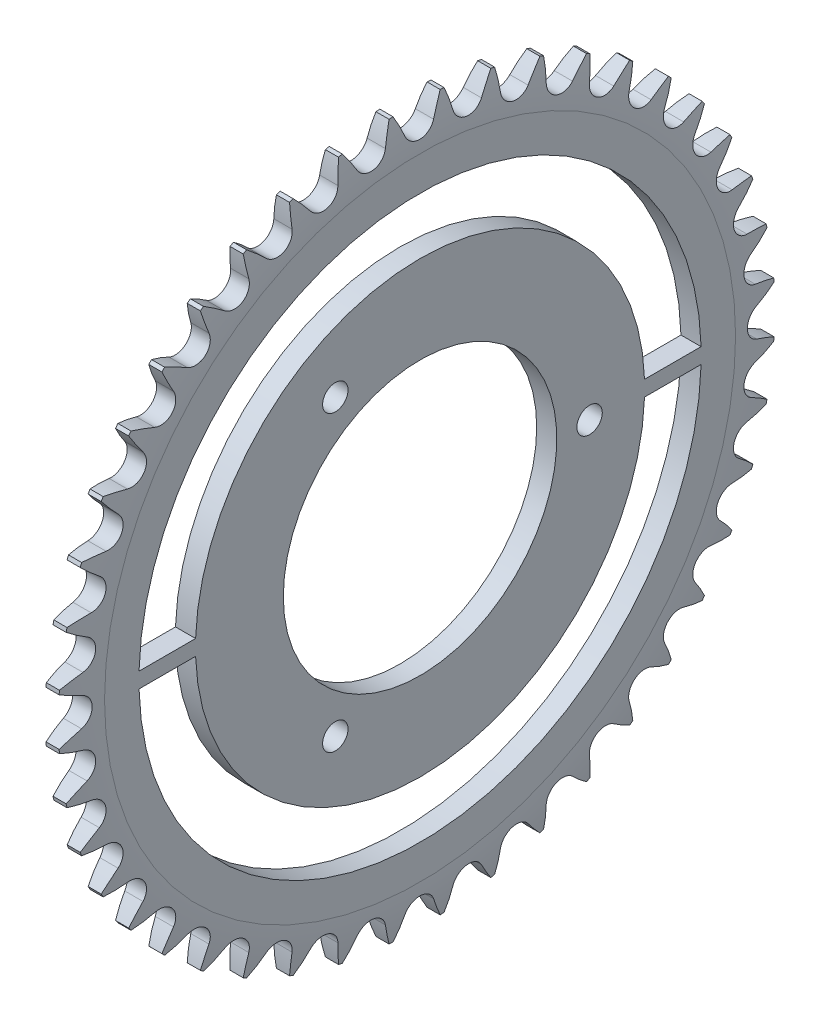
SolidWorks part; units mm, degrees
material "6061-T6 (SS)"
ref_plane "Plane1" through (0, 0, 0) normal (0, 0, 1) x (1, 0, 0)
ref_plane "Plane2" through (0, 0, 0) normal (0, 1, 0) x (1, 0, 0)
ref_plane "Plane3" through (0, 0, 0) normal (1, 0, 0) x (0, 0, -1)
sketch "Clipboard" plane through (0, 0, 0) normal (0, 1, 0) x (1, 0, 0)
  line L0 (0, 0) -> (4.166, -4.7924)
  line L1 (-15, 0) -> (100, 0) construction
  line L2 (0, 0) -> (-0.301, 0.3402)
  line L3 (0, 0) -> (-33.1636, 12.6754)
  line L4 (0, 0) -> (2.23, 2.1534)
  line L5 (0, 0) -> (-46.8476, -17.4728)
  line L6 (0, 0) -> (-2.1647, -1.4605)
  line L7 (-0.301, 0.3402) -> (35.1317, 35.773)
  line L8 (-76.2, 38.1) -> (-71.9, 38.1)
  line L9 (-73.4321, 41.7084) -> (-72.837, 41.7846)
  line L10 (-72.9336, 12.3402) -> (-58.5536, 12.3402)
  circle A0 centre (0, 0) radius 1.9875
  circle A1 centre (0, 0) radius 37.5
  circle A2 centre (0, 0) radius 37.5
  dimension "Num_teeth" = 44
  dimension "Thickness" = 2.6113
ref_axis "Axis1" through (0, 0, 0) along (1, 0, 0)
sketch "BasProSke" plane through (0, 0, 0) normal (0, 1, 0) x (1, 0, 0)
  line L0 (-10, 0) -> (60, 0) construction
  line L1 (0, 0) -> (0, 40.9511)
  line L2 (0, 0) -> (2.6113, 0)
  line L3 (2.6113, 0) -> (2.6113, 40.9511)
  line L4 (2.157, 46.4869) -> (0.4543, 46.4869)
  arc A0 (0, 40.9511) -> (0.4543, 46.4869) centre (33.9554, 40.9511) cw
  arc A1 (2.6113, 40.9511) -> (2.157, 46.4869) centre (-31.3441, 40.9511) ccw
  dimension "Thickness" = 2.6113
  dimension "Diameter" = 92.9739
  dimension "D1" = 5.5358
revolve "Base-Revolve" add sketch "BasProSke" angle 360 about L0
sketch "TooCutSke" plane through (0, 0, 0) normal (1, 0, 0) x (0, 0, -1)
  line L0 (0, 44.5256) -> (1.8738, 43.8054) construction
  line L1 (0, 0) -> (0, 107) construction
  line L2 (0, 44.5256) -> (-10, 44.5256) construction
  line L3 (0, 44.5256) -> (-1.8738, 43.8054) construction
  arc A0 (1.8738, 43.8054) -> (3.332, 46.8687) centre (22.3553, 35.934) cw
  arc A1 (1.8738, 43.8054) -> (-1.8738, 43.8054) centre (0, 44.5256) cw
  arc A2 (-1.8738, 43.8054) -> (-3.332, 46.8687) centre (-22.3553, 35.934) ccw
  arc A3 (3.332, 46.8687) -> (-3.332, 46.8687) centre (0, 0) ccw
extrude "ToothCut" cut sketch "TooCutSke" along normal through all
pattern_circular "TeethCuts" count 45 every 8.182 about axis through (-10, 0, 0) along (1, 0, 0) of "ToothCut"
ref_plane "FarPln" through (2.6113, 0, 0) normal (1, 0, 0) x (0, 0, -1)
sketch "BorSke" plane through (0, 0, 0) normal (1, 0, 0) x (0, 0, -1)
  circle A0 centre (0, 0) radius 17.75
  dimension "Diameter" = 35.5
extrude "Bore" cut sketch "BorSke" along normal mid plane 100.219
sketch "Sketch1" plane through (2.6113, 0, 0) normal (1, 0, 0) x (0, 0, -1)
  circle A0 centre (-11, 19.0526) radius 1.65
  circle A1 centre (22, 0) radius 1.65
  circle A2 centre (-11, -19.0526) radius 1.65
  point P10 (0, 0)
  point P19 (0, 0)
  dimension "D2" = 3.3
  dimension "D1" = 22
  dimension "D4" = 3
extrude "Cut-Extrude1" cut sketch "Sketch1" against normal blind 10
sketch "Sketch3" plane through (0, 0, 0) normal (-1, 0, 0) x (0, 0, 1)
  circle A0 centre (0, 0) radius 46.4869
  dimension "D1" = 92.9739
sketch "Sketch4" plane through (2.6113, 0, 0) normal (1, 0, 0) x (0, 0, -1)
  line L1 (0, 0) -> (29.15, 0) construction
  circle A0 centre (0, 0) radius 36.4869
  circle A1 centre (0, 0) radius 46.4869 construction
  circle A2 centre (0, 0) radius 29.15
  dimension "D1" = 10
  dimension "D2" = 29.15
extrude "Cut-Extrude2" cut sketch "Sketch4" against normal through all
sketch "Sketch5" plane through (2.6113, 0, 0) normal (1, 0, 0) x (0, 0, -1)
  line L1 (29.1328, 1) -> (36.4869, 1)
  line L2 (29.1328, 1) -> (29.1328, -1)
  line L3 (29.1328, -1) -> (36.4869, -1)
  line L4 (36.4869, 1) -> (36.4869, -1)
  circle A0 centre (0, 0) radius 29.15 construction
  circle A1 centre (0, 0) radius 36.4869 construction
  point P8 (29.1328, 0)
  dimension "D1" = 2
extrude "Boss-Extrude1" add sketch "Sketch5" against normal up to surface (2.6113 mm away) up to face at (0, 0, -17.75)
pattern_circular "CirPattern2" count 2 over 360 about axis through (0, 0, 0) along (1, 0, 0) of "Boss-Extrude1" reverse direction yes
equation "' \"Pitch@Clipboard\" = 12.7"
equation "' \"Num_strands@Clipboard\" = 1"
equation "' \"Num_teeth@Clipboard\" = 9"
equation "' \"Hub_dia@Clipboard\" = 50"
equation "' \"Overall_len@Clipboard\" = 3"
equation "' \"Diameter@BorSke\" = 12"
equation "' \"T_dim@Clipboard\" = 1"
equation "' \"Width@KeySke\" = 2"
equation "' \"Dr@Clipboard\" = 7.95"
equation "' \"Face_width@Clipboard\" = 7.3"
equation "' \"Side_radius@Clipboard\" = 12.7"
equation "' \"Side_relief@Clipboard\" = 1.27"
equation "' \"Transv_pitch@Clipboard\" = 14.38"
equation "' \"Show_teeth@Clipboard\" = 9"
equation "' \"Fillet_rad@Clipboard\" = 0.6"
equation "' \"Plate_wid@Clipboard\" = 12"
equation "\"MHD@Clipboard\" = \"Pitch@Clipboard\" * (1.0 / tan(3.14159265 / \"Num_teeth@Clipboard\" )) - 1.05 * \"Plate_wid@Clipboard\" - 2.0 * \"Fillet_rad@Clipboard\" - 1.0"
equation "\"OAL@Clipboard\" = \"Thickness@Clipboard\" + 2 * \"Fillet_rad@Clipboard\" + 1"
equation "\"MHD@Clipboard\" = ((sgn( \"MHD@Clipboard\" - \"Hub_dia@Clipboard\" )-1)*( \"MHD@Clipboard\" - \"Hub_dia@Clipboard\" ))/-2+ \"Hub_dia@Clipboard\""
equation "\"OAL@Clipboard\" = ((sgn( \"OAL@Clipboard\" - \"Overall_len@Clipboard\" )+1)*( \"OAL@Clipboard\" - \"Overall_len@Clipboard\" ))/2 + \"Overall_len@Clipboard\" + 0.0005"
equation "\"Num_teeth@TeethCuts\"=int( \"Num_teeth@Clipboard\" ) + 1"
equation "\"Num_teeth@TeethCuts\" = ((sgn( \"Num_teeth@TeethCuts\" - \"Num_teeth@Clipboard\" )-1)*( \"Num_teeth@TeethCuts\" - \"Num_teeth@Clipboard\" ))/-2+ \"Num_teeth@Clipboard\""
equation "\"Angle@TeethCuts\" = 360.0 / \"Num_teeth@Clipboard\""
equation "\"Seat_radius@TooCutSke\" = ( \"Pitch@Clipboard\" / 2.0) / sin(3.14159265 / \"Num_teeth@Clipboard\" ) - \"Dr@Clipboard\" / 2.0 + \"Dr@Clipboard\" * 0.505"
equation "\"R1@TooCutSke\"  = \"Dr@Clipboard\" * 0.505"
equation "\"X@TooCutSke\" = 140.0 - (90.0 / \"Num_teeth@Clipboard\")"
equation "\"R2@TooCutSke\" = 0.12 * \"Dr@Clipboard\" * ( \"Num_teeth@Clipboard\" + 2.0)"
equation "\"Overcut@TooCutSke\" = 0.5 + 0.625 * \"Pitch@Clipboard\" - 0.5 * \"Dr@Clipboard\"  +  \"Pitch@Clipboard\" / 2.0 / sin(3.14159265 / \"Num_teeth@Clipboard\" )"
equation "\"Diameter@BasProSke\" = 2.0 * ( 0.625 * \"Pitch@Clipboard\" - 0.5 * \"Dr@Clipboard\"  +  \"Pitch@Clipboard\" / 2.0 / sin(3.14159265 / \"Num_teeth@Clipboard\" ))"
equation "\"Thickness@BasProSke\"  = \"Thickness@Clipboard\""
equation "\"G1@BasProSke\"=\"Thickness@Clipboard\" * (127/730)"
equation "\"G2@BasProSke\"=\"Thickness@Clipboard\"*(127/730)"
equation "\"Length@HubNearOne\"= \"OAL@Clipboard\" - \"Thickness@BasProSke\""
equation "\"Diameter@HubNeaBotSke\"= \"MHD@Clipboard\""
equation "\"Length@HubNearBoth\"= ( \"OAL@Clipboard\" - \"Thickness@BasProSke\" ) / 2.0"
equation "\"D1@HubNearOneFillet\"= \"Fillet_rad@Clipboard\""
equation "\"D1@HubNearBothFillet\"= \"Fillet_rad@Clipboard\""
equation "\"Thickness@FarPln\" = \"Thickness@BasProSke\""
equation "\"Diameter@HubFarSke\"= \"MHD@Clipboard\""
equation "\"Length@HubFar\"= ( \"OAL@Clipboard\" - \"Thickness@BasProSke\" ) / 2.0"
equation "\"D1@HubFarFillet\"= \"Fillet_rad@Clipboard\""
equation "\"D1@Bore\" = \"OAL@Clipboard\" * 2.0"
equation "\"D1@Keyway\"= \"OAL@Clipboard\" * 2.0"
equation "\"Offset@KeySke\"= \"T_dim@Clipboard\" + \"Diameter@BorSke\" / 2.0"
equation "\"Side_radius@Clipboard\"=92.71/\"Thickness@Clipboard\""
equation "\"Side_relief@Clipboard\"=\"Thickness@Clipboard\" * (127/730)"
